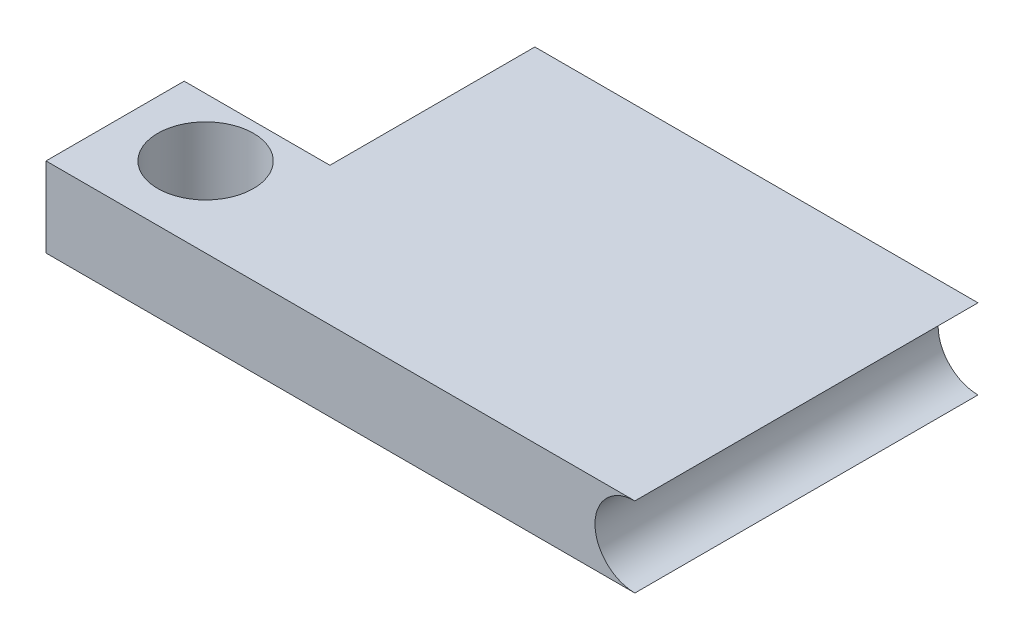
SolidWorks part; units mm, degrees
ref_plane "Front Plane" through (0, 0, 0) normal (0, 0, 1) x (1, 0, 0)
ref_plane "Top Plane" through (0, 0, 0) normal (0, 1, 0) x (1, 0, 0)
ref_plane "Right Plane" through (0, 0, 0) normal (1, 0, 0) x (0, 0, -1)
sketch "Sketch1" plane through (0, 0, 0) normal (0, 0, 1) x (1, 0, 0)
  line L0 (0, 150) -> (0, 0)
  line L1 (0, 150) -> (1106.9725, 150)
  line L3 (0, 0) -> (1106.9725, 0)
  line L4 (1106.9725, 150) -> (1106.9725, 0)
extrude "Boss-Extrude1" add sketch "Sketch1" along normal blind 645 contours L1 L4 L3 L0
sketch "Sketch2" plane through (0, 0, 0) normal (0, -1, 0) x (1, 0, 0)
  line L0 (0, 645) -> (0, 0) construction
  line L1 (0, 645) -> (1106.9725, 645) construction
  circle A0 centre (150, 495) radius 90
  dimension "D1" = 180
  dimension "D2" = 150
  dimension "D3" = 150
extrude "Cut-Extrude1" cut sketch "Sketch2" against normal through all contours A0
sketch "Sketch3" plane through (0, 0, 0) normal (0, -1, 0) x (1, 0, 0)
  line L1 (0, 0) -> (273.9363, 0)
  line L2 (0, 0) -> (0, 385.2587)
  line L3 (0, 385.2587) -> (273.9363, 385.2587)
  line L4 (273.9363, 0) -> (273.9363, 385.2587)
extrude "Cut-Extrude2" cut sketch "Sketch3" against normal through all
sketch "Sketch4" plane through (0, 0, 645) normal (0, 0, 1) x (1, 0, 0)
  line L0 (1106.9725, 150) -> (1106.9725, 0) construction
  line L1 (1106.9725, 150) -> (1106.9725, 0)
  arc A0 (1106.9725, 0) -> (1106.9725, 150) centre (1106.9725, 75) cw
  dimension "D1" = 75
extrude "Cut-Extrude3" cut sketch "Sketch4" against normal through all contours L1 A0
